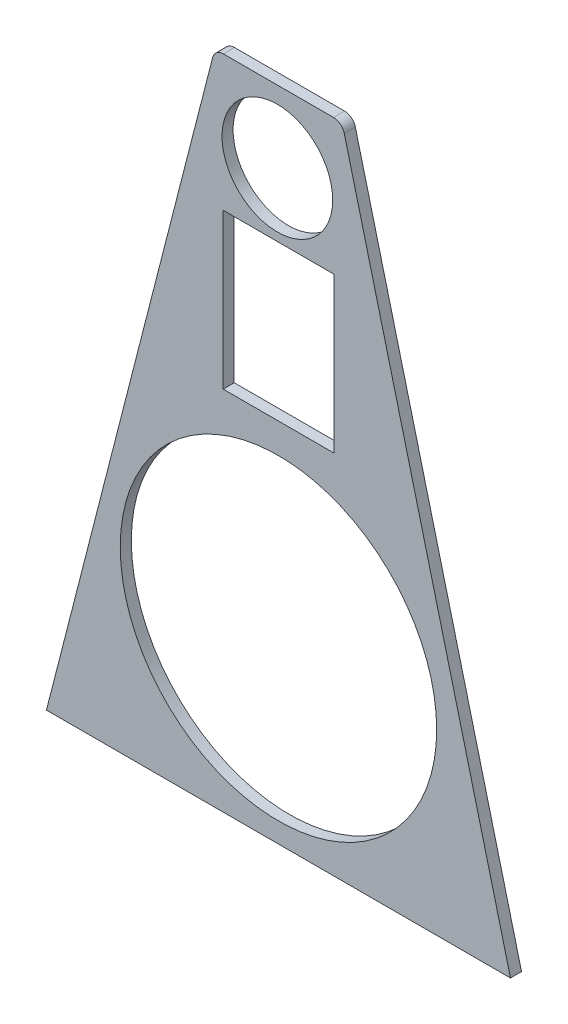
SolidWorks part; units mm, degrees
material "6061 Alloy"
ref_plane "Front" through (0, 0, 0) normal (0, 0, 1) x (1, 0, 0)
ref_plane "Top" through (0, 0, 0) normal (0, 1, 0) x (1, 0, 0)
ref_plane "Right" through (0, 0, 0) normal (1, 0, 0) x (0, 0, -1)
sketch "Sketch3" plane through (0, 0, 0) normal (0, 0, 1) x (1, 0, 0)
  line L1 (1113.7127, -1694.2708) -> (362.5166, 1235.9362)
  line L3 (-231.8855, 1235.9362) -> (-983.0816, -1694.2708)
  line L4 (65.3155, 1273.5196) -> (65.3155, -1694.2708) construction
  line L10 (-983.0816, -1694.2708) -> (1113.7127, -1694.2708)
  line L17 (-183.4518, 1273.5196) -> (314.0829, 1273.5196)
  line L19 (-184.6845, -38.8919) -> (315.3155, -38.8919)
  line L20 (-184.6845, -38.8919) -> (-184.6845, 661.1081)
  line L21 (-184.6845, 661.1081) -> (315.3155, 661.1081)
  line L22 (315.3155, -38.8919) -> (315.3155, 661.1081)
  line L24 (-184.6845, -38.8919) -> (315.3155, 661.1081) construction
  line L25 (-184.6845, 661.1081) -> (315.3155, -38.8919) construction
  arc A10 (-231.8855, 1235.9362) -> (-183.4518, 1273.5196) centre (-183.4518, 1223.5196) cw
  arc A11 (362.5166, 1235.9362) -> (314.0829, 1273.5196) centre (314.0829, 1223.5196) ccw
  circle A13 centre (60.2947, 948.3527) radius 250
  circle A14 centre (65.3155, -888.8919) radius 715
  point P1 (65.3155, 311.1081)
  point P11 (60.2939, 331.5151)
  point P28 (-222.2506, 1273.5196)
  point P33 (352.8817, 1273.5196)
  dimension "D4" = 500
  dimension "D5" = 700
  dimension "D6" = 500
  dimension "D9" = 50
  dimension "D11" = 50
  dimension "D2" = 1430
  dimension "D3" = 1200
extrude "Boss-Extrude1" add sketch "Sketch3" along normal blind 50 contours L3 L1 region at (65.3155, -1657.9331, 0)
